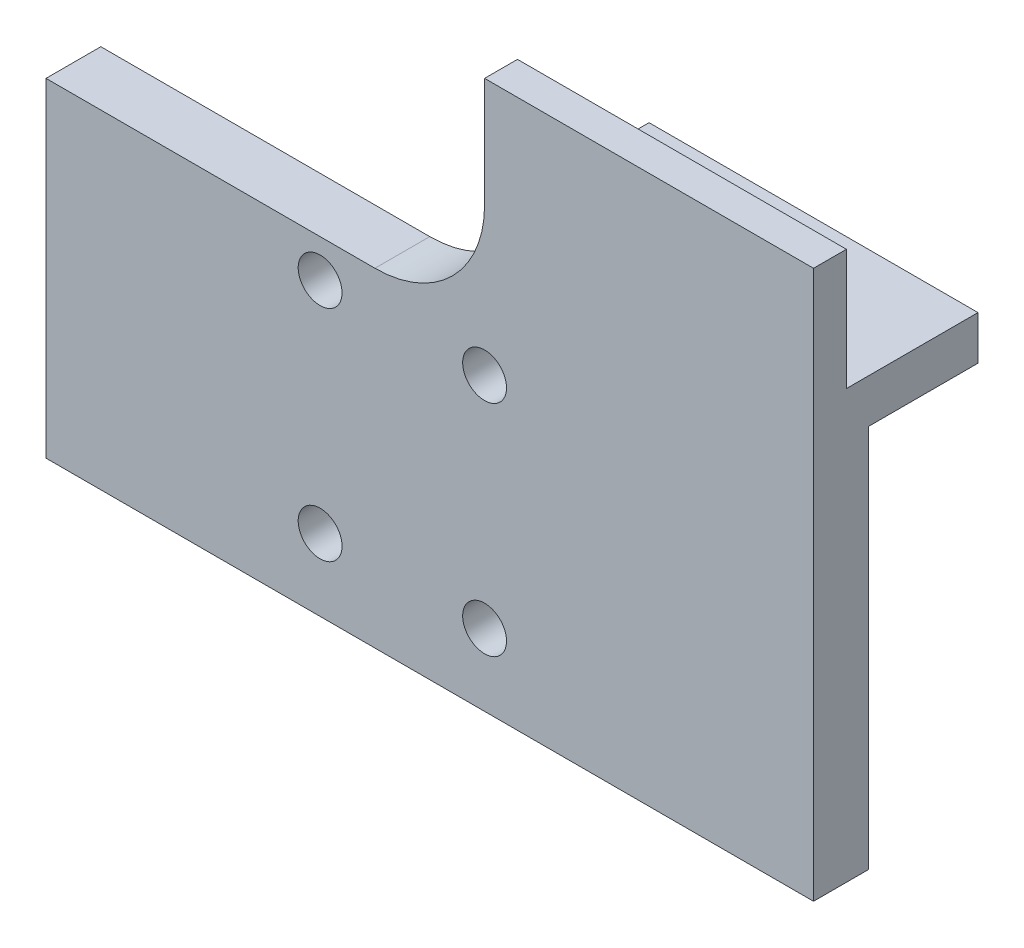
SolidWorks part; units mm, degrees
ref_plane "Front Plane" through (0, 0, 0) normal (0, 0, 1) x (1, 0, 0)
ref_plane "Top Plane" through (0, 0, 0) normal (0, 1, 0) x (1, 0, 0)
ref_plane "Right Plane" through (0, 0, 0) normal (1, 0, 0) x (0, 0, -1)
sketch "Sketch1" plane through (0, 0, 0) normal (0, 0, 1) x (1, 0, 0)
  line L0 (0, 0) -> (70, 0)
  line L1 (0, 0) -> (0, 30)
  line L2 (0, 30) -> (30, 30)
  line L4 (70, 50) -> (70, 0)
  line L5 (40, 40) -> (40, 50)
  line L6 (40, 50) -> (70, 50)
  arc A0 (30, 30) -> (40, 40) centre (30, 40) ccw
  point P6 (40, 45.0006)
  dimension "D2" = 10
  dimension "D3" = 50
  dimension "D1" = 70
  dimension "D5" = 30
  dimension "D6" = 30
extrude "Body" add sketch "Sketch1" along normal blind 5
sketch "Sketch2" plane through (0, 0, 5) normal (0, 0, 1) x (1, 0, 0)
  line L1 (0, 0) -> (70, 0) construction
  circle A0 centre (25, 6.55) radius 2
  circle A1 centre (40, 6.55) radius 2
  point P6 (0, 0)
  dimension "D1" = 15
  dimension "D2" = 4
  dimension "D3" = 25
  dimension "D4" = 6.55
extrude "Cut-Extrude1" cut sketch "Sketch2" against normal through all
pattern_linear "LPattern1" count 2 spacing 20 along (0, 1, 0) of "Cut-Extrude1"
sketch "Sketch4" plane through (0, 50, 0) normal (0, 1, 0) x (1, 0, 0)
  line L0 (70, -5) -> (70, 0) construction
  line L1 (40, 0) -> (70, 0)
  line L2 (40, 0) -> (40, -2)
  line L3 (40, -2) -> (70, -2)
  line L4 (70, 0) -> (70, -2)
  dimension "D1" = 2
extrude "Cut-Extrude2" cut sketch "Sketch4" against normal blind 12
sketch "Sketch5" plane through (0, 0, 2) normal (0, 0, -1) x (-1, 0, 0)
  line L0 (-40, 40) -> (-40, 50) construction
  line L1 (-70, 38) -> (-40, 38)
  line L2 (-70, 38) -> (-70, 39)
  line L3 (-70, 39) -> (-40, 39)
  line L4 (-40, 38) -> (-40, 39)
  dimension "D1" = 1
extrude "Boss-Extrude3" add sketch "Sketch5" along normal blind 12
sketch "Sketch6" plane through (0, 38, 0) normal (0, -1, 0) x (1, 0, 0)
  line L4 (70, -10) -> (70, 0)
  line L5 (70, 0) -> (40, 0)
  line L6 (40, 0) -> (40, -10)
  line L7 (40, -10) -> (70, -10)
  line L8 (70, -10) -> (70, 0)
  line L9 (70, 0) -> (40, 0)
  line L10 (40, 0) -> (40, -10)
  line L11 (40, -10) -> (70, -10)
  dimension "D1" = 0
extrude "Boss-Extrude4" add sketch "Sketch6" along normal blind 3
